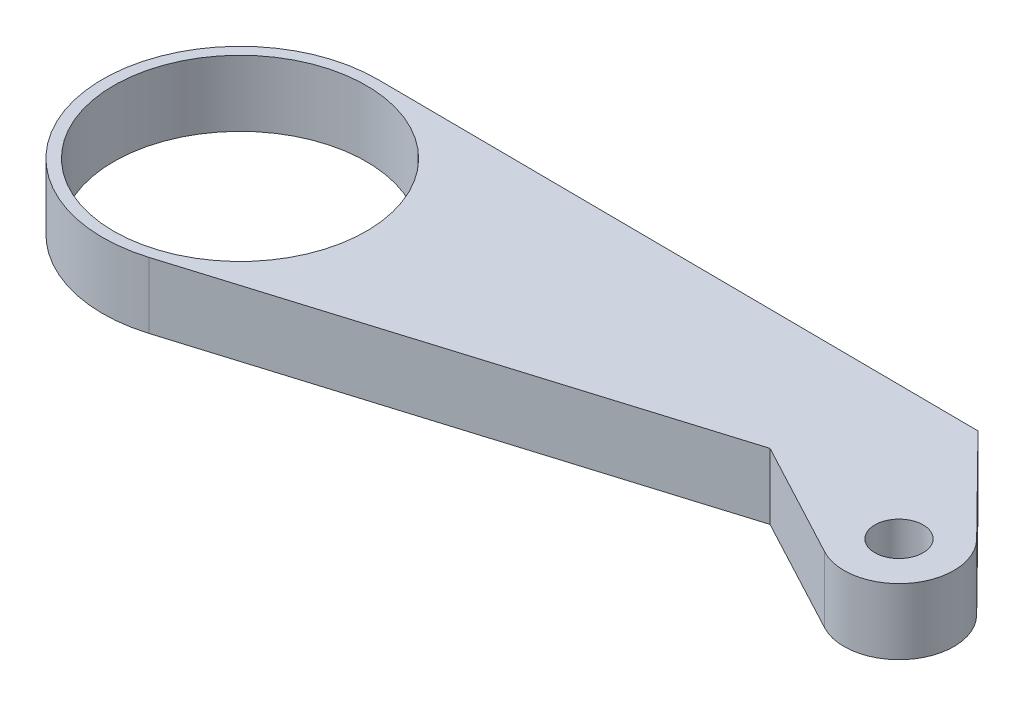
SolidWorks part; units mm, degrees
ref_plane "Front Plane" through (0, 0, 0) normal (0, 0, 1) x (1, 0, 0)
ref_plane "Top Plane" through (0, 0, 0) normal (0, 1, 0) x (1, 0, 0)
ref_plane "Right Plane" through (0, 0, 0) normal (1, 0, 0) x (0, 0, -1)
ref_plane "Plane1" through (0, -40, 0) normal (0, 1, 0) x (1, 0, 0)
sketch "Sketch1" plane through (0, -40, 0) normal (0, 1, 0) x (1, 0, 0)
  line L0 (0, 0) -> (300, 0) construction
  line L1 (0, 0) -> (0, 62.5) construction
  line L2 (0.4468, 62.4984) -> (18.2292, -59.7825) construction
  line L3 (317.8036, 17.5508) -> (288.2469, -22.065) construction
  line L4 (300, 0) -> (300, 25) construction
  line L5 (0.4468, 62.4984) -> (409.655, 59.573)
  line L6 (409.655, 59.573) -> (18.2292, -59.7825)
  line L7 (288.2469, -22.065) -> (234.9772, 6.3094)
  line L8 (317.8036, 17.5508) -> (275.4321, 60.5325)
  line L9 (275.4321, 60.5325) -> (234.9772, 6.3094) construction
  circle A0 centre (0, 0) radius 62.5
  circle A1 centre (300, 0) radius 11
  circle A2 centre (300, 0) radius 25
  circle A3 centre (0, 0) radius 57.5
  point P11 (307.1813, 28.3262)
  point P14 (0, 0)
  dimension "D2" = 125
  dimension "D3" = 22
  dimension "D4" = 50
  dimension "D7" = 115
  dimension "D1" = 300
  dimension "D5" = 135
  dimension "D6" = 135
extrude "Boss-Extrude2" add sketch "Sketch1" along normal blind 30 contours A0 A3 | A2 L8 L6 | A2 L6 L7 | A0 L6 L8 L5 | A2 A1 region at (151.1228, -40, -21.8113) region at (43.0974, -40, -42.7904) region at (306.3702, -40, -25.1268) region at (263.8681, -40, -3.506) region at (305.9699, -40, -23.5479)
